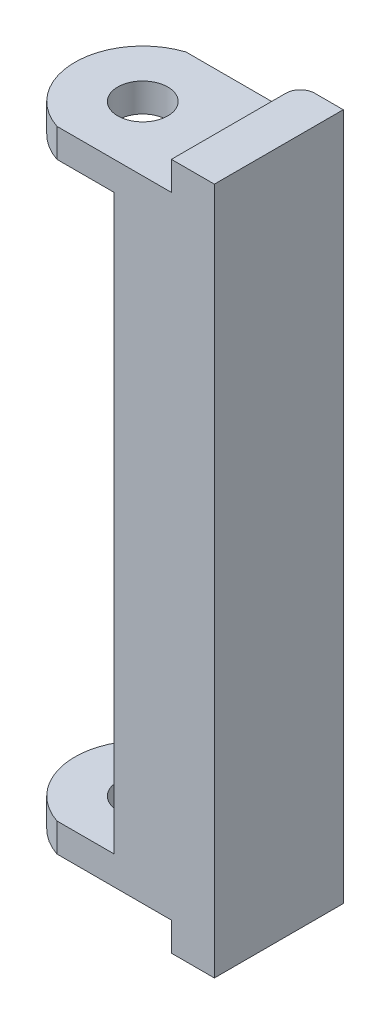
SolidWorks part; units mm, degrees
ref_plane "Front Plane" through (0, 0, 0) normal (0, 0, 1) x (1, 0, 0)
ref_plane "Top Plane" through (0, 0, 0) normal (0, 1, 0) x (1, 0, 0)
ref_plane "Right Plane" through (0, 0, 0) normal (1, 0, 0) x (0, 0, -1)
sketch "Sketch1" plane through (0, 0, 0) normal (0, 1, 0) x (1, 0, 0)
  line L0 (-2.5, 0) -> (2.5, 0) construction
  line L5 (-3.991, 4.5) -> (4, 4.5)
  line L6 (-3.991, -4.5) -> (4, -4.5)
  line L8 (7, -4.5) -> (7, 4.5)
  line L10 (5, 4.5) -> (4, 4.5)
  line L11 (7, -4.5) -> (4, -4.5)
  line L12 (7, -4.5) -> (7, 4.5)
  line L13 (7, 4.5) -> (5, 4.5)
  line L14 (4, -4.5) -> (4, 3.5)
  arc A1 (-3.991, 4.5) -> (-3.991, -4.5) centre (-2.5, 0) ccw
  circle A3 centre (-2.5, 0) radius 1.75
  arc A4 (0.0045, 4.5) -> (0.0045, -4.5) centre (-2.5, 0) cw
  arc A5 (5, 4.5) -> (4, 3.5) centre (5, 3.5) ccw
  point P2 (0, 0)
  point P4 (0, 0)
  dimension "D2" = 9.5
  dimension "D3" = 3.5
  dimension "D6" = 5.15
  dimension "D8" = 1
  dimension "D1" = 9
  dimension "D4" = 5
  dimension "D7" = 3
extrude "Boss-Extrude3" add sketch "Sketch1" along normal blind 2 contours A4 L5 A1 L6 A3 | L5 A4 L6 | L12 L11 L14 A5 L13 region at (-1.9933, 0, -4.3663) region at (2.8287, 0, -0.0477)
extrude "Boss-Extrude4" add sketch "Sketch1<3>" against normal blind 20 contours L5 A4 L6 | L12 L11 L14 A5 L13 region at (2.8287, 0, -0.0477)
sketch "Sketch1<3>" plane through (0, 0, 0) normal (0, 1, 0) x (1, 0, 0) same geometry as "Sketch1"
extrude "Boss-Extrude5" add sketch "Sketch1<5>" along normal blind 4 contours L13 A5 L14 L11 L8 region at (5.5102, 0, 0.0343)
sketch "Sketch1<5>" plane through (0, 0, 0) normal (0, 1, 0) x (1, 0, 0) same geometry as "Sketch1"
mirror "Mirror1" about plane through (0, -20, 0) normal (0, 1, 0) of bodies 111
